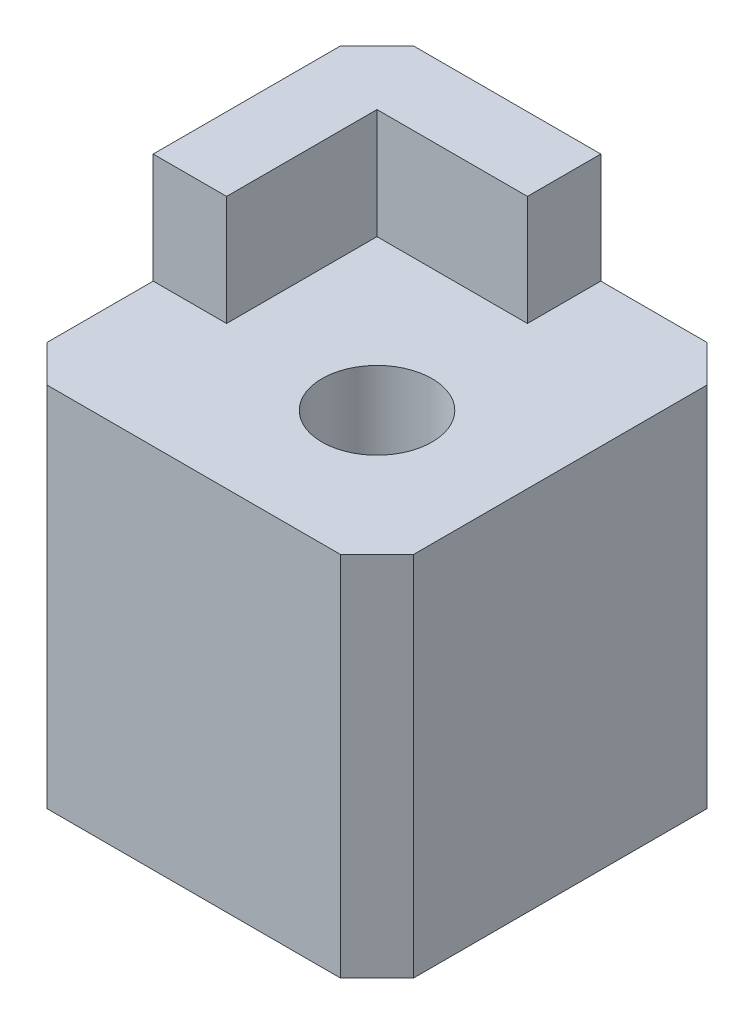
SolidWorks part; units mm, degrees
ref_plane "Front Plane" through (0, 0, 0) normal (0, 0, 1) x (1, 0, 0)
ref_plane "Top Plane" through (0, 0, 0) normal (0, 1, 0) x (1, 0, 0)
ref_plane "Right Plane" through (0, 0, 0) normal (1, 0, 0) x (0, 0, -1)
sketch "Sketch1" plane through (0, 0, 0) normal (0, 1, 0) x (1, 0, 0)
  line L0 (0, 4.1) -> (-4.1, 4.1)
  line L1 (-4.1, 4.1) -> (-4.1, 0)
  line L2 (-4.1, 0) -> (-6.1, 0)
  line L3 (-6.1, 0) -> (-6.1, 6.1)
  line L4 (-6.1, 6.1) -> (0, 6.1)
  line L5 (0, 6.1) -> (0, 4.1)
  line L7 (-6.1, 6.1) -> (3.9, 6.1)
  line L8 (-6.1, 6.1) -> (-6.1, -3.9)
  line L9 (-6.1, -3.9) -> (3.9, -3.9)
  line L10 (3.9, 6.1) -> (3.9, -3.9)
  circle A0 centre (0, 0) radius 1.5
  dimension "D1" = 3
  dimension "D2" = 4.1
  dimension "D3" = 4.1
  dimension "D4" = 2
  dimension "D5" = 10
extrude "Boss-Extrude1" add sketch "Sketch1" against normal blind 10 contours L7 L10 L9 L8
extrude "Boss-Extrude2" add sketch "Sketch1<3>" along normal blind 3 contours L5 L4 L3 L2 L1 L0 region at (-2.05, 0, -4.1863)
sketch "Sketch1<3>" plane through (0, 0, 0) normal (0, 1, 0) x (1, 0, 0) same geometry as "Sketch1"
chamfer "Chamfer1" distance 1 angle 45 4 edges at (-6.1, -3.5, -6.1) (3.9, -5, -6.1) (-6.1, -5, 3.9) (3.9, -5, 3.9)
extrude "Cut-Extrude1" cut sketch "Sketch1<4>" against normal through all contours A0 region at (0, 0, 0)
sketch "Sketch1<4>" plane through (0, 0, 0) normal (0, 1, 0) x (1, 0, 0) same geometry as "Sketch1"
cosmetic thread "Cosmetic Thread1" parameters "D2"=4
